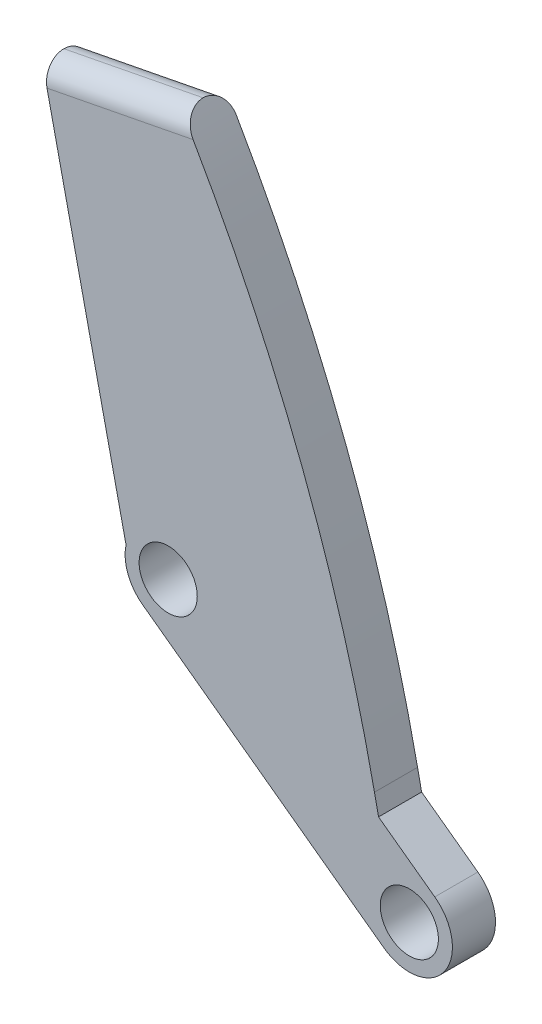
SolidWorks part; units mm, degrees
ref_plane "Front Plane" through (0, 0, 0) normal (0, 0, 1) x (1, 0, 0)
ref_plane "Top Plane" through (0, 0, 0) normal (0, 1, 0) x (1, 0, 0)
ref_plane "Right Plane" through (0, 0, 0) normal (1, 0, 0) x (0, 0, -1)
sketch "Sketch1" plane through (0, 0, 0) normal (0, 0, 1) x (1, 0, 0)
  line L1 (-24.7479, 13.1495) -> (-2.3618, -3.2283)
  line L2 (-20.0243, 19.606) -> (2.3618, 3.2283)
  circle A0 centre (0, 0) radius 2.7
  arc A1 (-2.3618, -3.2283) -> (2.3618, 3.2283) centre (0, 0) ccw
  circle A2 centre (-22.3861, 16.3777) radius 2.7
  arc A3 (-20.0243, 19.606) -> (-24.7479, 13.1495) centre (-22.3861, 16.3777) ccw
  dimension "D1" = 8
  dimension "D2" = 5.4
  dimension "D3" = 27.7375
extrude "Boss-Extrude1" add sketch "Sketch1" along normal blind 4
sketch "Sketch2" plane through (0, 0, 4) normal (0, 0, 1) x (1, 0, 0)
  line L3 (-22.3861, 16.3777) -> (0, 0) construction
  line L10 (-26.2997, 17.2045) -> (-34.0691, 52.2061)
  line L11 (-2.8588, 7.0477) -> (-13.2317, 56.3866)
  line L16 (2.3618, 3.2283) -> (-20.0243, 19.606) construction
  line L19 (-21.1435, 54.7232) -> (-34.0691, 52.2061)
  line L22 (-20.0243, 19.606) -> (-13.3544, 14.7263)
  line L23 (-21.1435, 54.7232) -> (-13.2317, 56.3866)
  line L24 (-13.3544, 14.7263) -> (-2.8588, 7.0477)
  arc A1 (-20.0243, 19.606) -> (-26.2997, 17.2045) centre (-22.3861, 16.3777) ccw
extrude "Boss-Extrude2" add sketch "Sketch2" against normal through all
fillet "Fillet4" radius 150 1 edges at (-13.2317, 56.3866, 2)
fillet "Fillet5" radius 2 2 edges at (-27.6063, 53.4647, 4) (-27.6063, 53.4647, 0)
